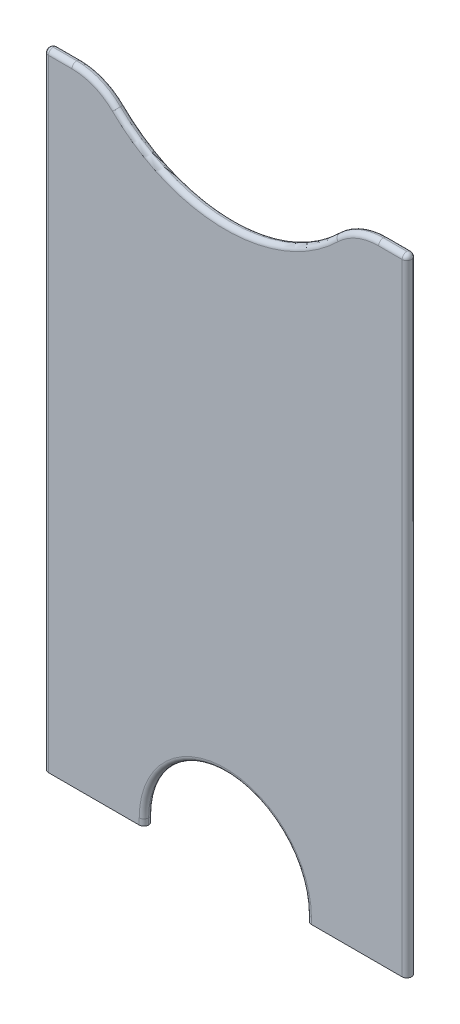
SolidWorks part; units mm, degrees
ref_plane "Front Plane" through (0, 0, 0) normal (0, 0, 1) x (1, 0, 0)
ref_plane "Top Plane" through (0, 0, 0) normal (0, 1, 0) x (1, 0, 0)
ref_plane "Right Plane" through (0, 0, 0) normal (1, 0, 0) x (0, 0, -1)
sketch "Sketch1" plane through (0, 0, 0) normal (0, 1, 0) x (1, 0, 0)
  line L0 (-28.25, 0) -> (28.25, 0)
  line L1 (28.25, 1.5) -> (-28.25, 1.5)
  arc A0 (28.25, 0) -> (28.25, 1.5) centre (28.25, 0.75) ccw
  arc A1 (-28.25, 1.5) -> (-28.25, 0) centre (-28.25, 0.75) ccw
  point P8 (0, 0)
  dimension "D2" = 0.75
  dimension "D1" = 56.5
extrude "Boss-Extrude1" add sketch "Sketch1" along normal blind 100 contours L0 A0 L1 A1
sketch "Sketch2" plane through (0, 0, 0) normal (0, 0, 1) x (1, 0, 0)
  line L2 (-20, 100) -> (20, 100)
  line L3 (-28.25, 100) -> (28.25, 100) construction
  arc A0 (-20, 100) -> (20, 100) centre (0, 115) ccw
  dimension "D1" = 25
  dimension "D2" = 40
extrude "Cut-Extrude1" cut sketch "Sketch2" against normal through all both and the other way through all
sketch "Sketch3" plane through (0, 0, 0) normal (0, 0, 1) x (1, 0, 0)
  line L1 (-28.25, 0) -> (28.25, 0) construction
  line L2 (13, 1) -> (13, 0)
  line L3 (13, 0) -> (-13, 0)
  line L4 (-13, 1) -> (-13, 0)
  arc A0 (-13, 1) -> (13, 1) centre (0, 1) cw
  point P7 (0, 0)
  dimension "D2" = 1
  dimension "D1" = 26
extrude "Cut-Extrude2" cut sketch "Sketch3" against normal blind 10
fillet "Fillet6" radius 10 1 edges at (-20, 100, -0.75)
fillet "Fillet7" radius 10 1 edges at (20, 100, -0.75)
fillet "Fillet13" radius 0.75 12 edges at (20.7153, 99.2582, 0) (-20.7153, 99.2582, 0) (20.7153, 99.2582, -1.5) (-20.7153, 99.2582, -1.5) (29, 100, -0.75) (26.3724, 100, 0) (26.3724, 100, -1.5) (0, 90, -1.5) (0, 90, 0) (-29, 100, -0.75) (-26.3724, 100, -1.5) (-26.3724, 100, 0)
fillet "Fillet14" radius 0.75 6 edges at (13, 0.5, -1.5) (-13, 0.5, -1.5) (13, 0.5, 0) (-13, 0.5, 0) (0, 14, -1.5) (0, 14, 0)
